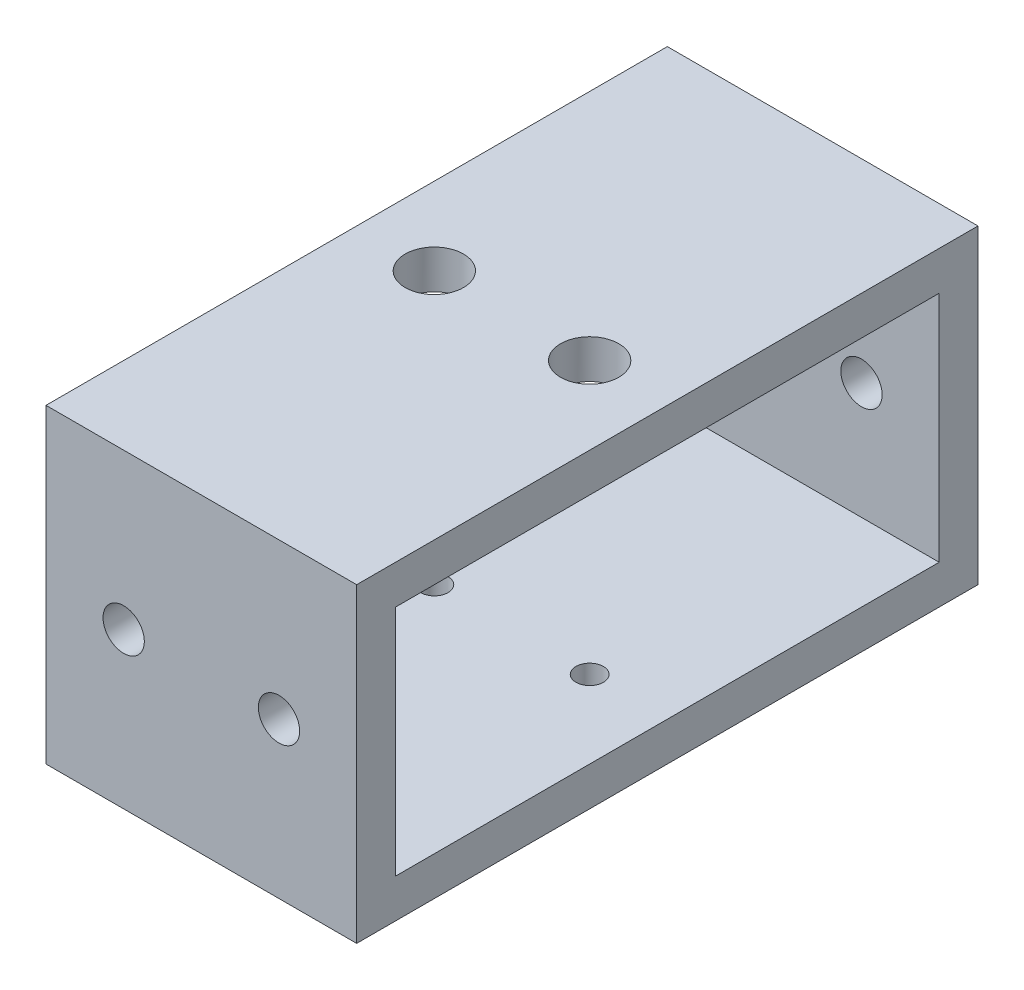
SolidWorks part; units mm, degrees
ref_plane "Front Plane" through (0, 0, 0) normal (0, 0, 1) x (1, 0, 0)
ref_plane "Top Plane" through (0, 0, 0) normal (0, 1, 0) x (1, 0, 0)
ref_plane "Right Plane" through (0, 0, 0) normal (1, 0, 0) x (0, 0, -1)
sketch "Sketch2" plane through (0, 0, 0) normal (1, 0, 0) x (0, 0, -1)
  line L9 (-50.8, -25.4) -> (50.8, -25.4)
  line L10 (-50.8, -25.4) -> (-50.8, 25.4)
  line L11 (-50.8, 25.4) -> (50.8, 25.4)
  line L12 (50.8, -25.4) -> (50.8, 25.4)
  line L13 (-50.8, -25.4) -> (50.8, 25.4) construction
  line L14 (-50.8, 25.4) -> (50.8, -25.4) construction
  line L15 (-44.45, -19.05) -> (44.45, -19.05)
  line L16 (-44.45, -19.05) -> (-44.45, 19.05)
  line L17 (-44.45, 19.05) -> (44.45, 19.05)
  line L18 (44.45, -19.05) -> (44.45, 19.05)
  line L19 (-44.45, -19.05) -> (44.45, 19.05) construction
  line L20 (-44.45, 19.05) -> (44.45, -19.05) construction
  point P0 (0, 0)
  point P5 (0, 0)
  dimension "D1" = 6.35
  dimension "D2" = 101.6
  dimension "D3" = 50.8
  dimension "D4" = 6.35
extrude "Boss-Extrude1" add sketch "Sketch2" along normal mid plane 50.8
sketch "Sketch3" plane through (0, 0, 50.8) normal (0, 0, 1) x (1, 0, 0)
  line L0 (-12.7, 0) -> (12.7, 0)
  point P4 (0, 0)
  dimension "D1" = 25.4
hole_wizard "1/4 Clearance Hole1" positions "Sketch4" profile "Sketch5" hole size "1/4" standard "ANSI Inch" end condition through all
sketch "Sketch4" plane through (0, 0, 50.8) normal (0, 0, 1) x (1, 0, 0)
  point P0 (-12.7, 0)
  point P3 (12.7, 0)
sketch "Sketch5" plane through (-12.7, 0, 50.8) normal (1, 0, 0) x (0, -1, 0)
  line L0 (0, 0) -> (0, 101.6)
  line L1 (0, 101.6) -> (3.3782, 101.6)
  line L2 (3.3782, 101.6) -> (3.3782, 0)
  line L5 (3.3782, 0) -> (0, 0)
  line L11 (0, -6.35) -> (0, 107.95) construction
  dimension "Thru Hole Dia." = 6.7564
  dimension "Thru Hole Depth" = 101.6
sketch "Sketch6" plane through (0, -19.05, 0) normal (0, 1, 0) x (1, 0, 0)
  line L0 (25.4, 0) -> (-25.4, 0) construction
  line L1 (25.4, -44.45) -> (25.4, 44.45) construction
  line L2 (-25.4, -44.45) -> (-25.4, 44.45) construction
  line L3 (6.35, 0) -> (19.05, 0)
  point P9 (12.7, 0)
  point P10 (0, 0)
  dimension "D1" = 12.7
  dimension "D2" = 12.7
hole_wizard "#8 Clearance Hole1" positions "Sketch7" profile "Sketch8" hole size "#8" standard "ANSI Inch" end condition through all
sketch "Sketch7" plane through (0, -19.05, 0) normal (0, 1, 0) x (1, 0, 0)
  point P0 (12.7, 0)
sketch "Sketch8" plane through (12.7, -19.05, 0) normal (1, 0, 0) x (0, 0, 1)
  line L0 (0, 0) -> (0, 6.35)
  line L1 (0, 6.35) -> (2.2479, 6.35)
  line L2 (2.2479, 6.35) -> (2.2479, 0)
  line L5 (2.2479, 0) -> (0, 0)
  line L11 (0, -6.35) -> (0, 107.95) construction
  dimension "Thru Hole Dia." = 4.4958
  dimension "Thru Hole Depth" = 6.35
mirror "Mirror1" about plane through (0, 0, 0) normal (1, 0, 0) of "#8 Clearance Hole1"
hole_wizard "3/8 (0.375) Diameter Hole1" positions "Sketch10" profile "Sketch11" hole size "3/8" standard "ANSI Inch" end condition up to next
sketch "Sketch10" plane through (0, 25.4, 0) normal (0, 1, 0) x (1, 0, 0)
  circle A0 centre (-12.7, 0) radius 2.2479 construction
  circle A2 centre (12.7, 0) radius 2.2479 construction
  point P0 (-12.7, 0)
  point P3 (12.7, 0)
sketch "Sketch11" plane through (-12.7, 25.4, 0) normal (1, 0, 0) x (0, 0, 1)
  line L0 (0, 0) -> (0, 6.35)
  line L1 (0, 6.35) -> (4.7625, 6.35)
  line L2 (4.7625, 6.35) -> (4.7625, 0)
  line L5 (4.7625, 0) -> (0, 0)
  line L11 (0, -6.35) -> (0, 107.95) construction
  dimension "Thru Hole Dia." = 9.525
  dimension "Thru Hole Depth" = 6.35
equation "\"wall\"=0.25"
equation "\"D1@Sketch2\"=\"wall\""
equation "\"Width\"=4"
equation "\"D2@Sketch2\"=\"Width\""
equation "\"Height\"=2"
equation "\"D3@Sketch2\"=\"Height\""
equation "\"D4@Sketch2\"=\"wall\""
equation "\"Length\"=2"
equation "\"D1@Boss-Extrude1\"=\"Length\""
equation "\"D2@Sketch6\"=\"Length\"/4"
equation "\"D1@Sketch6\"=\"Length\"/4"
